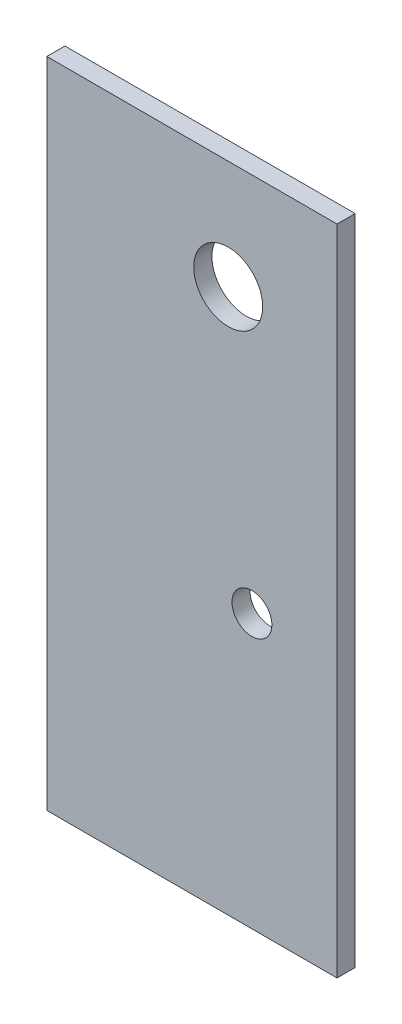
SolidWorks part; units mm, degrees
material "Thornel Mat VMA"
ref_plane "Front Plane" through (0, 0, 0) normal (0, 0, 1) x (1, 0, 0)
ref_plane "Top Plane" through (0, 0, 0) normal (0, 1, 0) x (1, 0, 0)
ref_plane "Right Plane" through (0, 0, 0) normal (1, 0, 0) x (0, 0, -1)
sketch "Sketch1" plane through (0, 0, 0) normal (0, 0, 1) x (1, 0, 0)
  line L0 (0, 103.759) -> (0, -103.759) construction
  line L1 (-30, 76) -> (50, 76)
  line L2 (-30, 76) -> (-30, 256)
  line L3 (-30, 256) -> (50, 256)
  line L4 (50, 76) -> (50, 256)
  circle A0 centre (20, 226) radius 9.5
  dimension "D1" = 150
  dimension "D5" = 19
  dimension "D2" = 20
  dimension "D3" = 180
  dimension "D4" = 80
extrude "Boss-Extrude1" add sketch "Sketch1" along normal blind 5
sketch "Sketch2" plane through (0, 0, 5) normal (0, 0, 1) x (1, 0, 0)
  line L0 (20, 226) -> (26.5367, 151.2854) construction
  line L1 (20, 226) -> (-17.1819, 226) construction
  circle A0 centre (26.5367, 151.2854) radius 5.5
  dimension "D3" = 11
  dimension "D1" = 75
  dimension "D2" = 95
extrude "Cut-Extrude1" cut sketch "Sketch2" against normal blind 30
